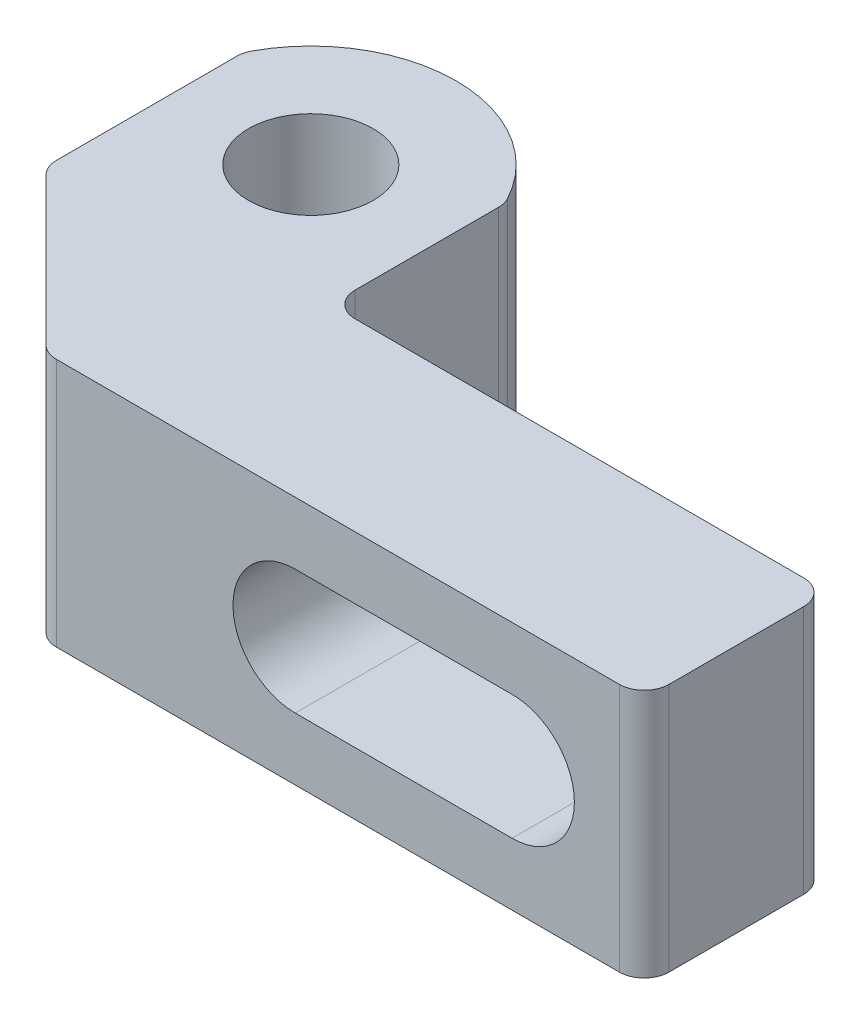
SolidWorks part; units mm, degrees
ref_plane "Front Plane" through (0, 0, 0) normal (0, 0, 1) x (1, 0, 0)
ref_plane "Top Plane" through (0, 0, 0) normal (0, 1, 0) x (1, 0, 0)
ref_plane "Right Plane" through (0, 0, 0) normal (1, 0, 0) x (0, 0, -1)
sketch "Sketch1" plane through (0, 0, 0) normal (0, 1, 0) x (1, 0, 0)
  line L0 (0, 0) -> (0, 7.4)
  line L1 (0, 7.4) -> (-20, 7.4)
  line L2 (-20, 7.4) -> (-20, 14.4)
  line L3 (0, 0) -> (-24, 0)
  line L4 (-24, 0) -> (-30.5, 6.5)
  line L5 (-30.5, 6.5) -> (-30.5, 14.4)
  line L6 (-30.5, 14.4) -> (-20, 14.4) construction
  arc A0 (-30.5, 14.4) -> (-20, 14.4) centre (-25.25, 11.8739) cw
  circle A1 centre (-25.25, 11.8739) radius 2.5
  dimension "D7" = 3.3
  dimension "D8" = 5
  dimension "D1" = 7.4
  dimension "D2" = 10.5
  dimension "D3" = 20
  dimension "D4" = 24
  dimension "D5" = 135
  dimension "D6" = 7
extrude "Boss-Extrude1" add sketch "Sketch1" along normal blind 10
sketch "Sketch3" plane through (0, 0, -7.4) normal (0, 0, -1) x (-1, 0, 0)
  line L0 (20, 5) -> (0, 5) construction
  line L1 (20, 10) -> (20, 0) construction
  line L2 (0, 10) -> (0, 0) construction
  line L3 (14, 5) -> (5.3, 5) construction
  line L4 (14, 2.5) -> (5.3, 2.5)
  line L5 (14, 7.5) -> (5.3, 7.5)
  arc A0 (14, 2.5) -> (14, 7.5) centre (14, 5) ccw
  arc A1 (5.3, 7.5) -> (5.3, 2.5) centre (5.3, 5) ccw
  point P8 (9.65, 5)
  point P13 (4.008, 5)
  dimension "D1" = 5
  dimension "D2" = 2.8
  dimension "D3" = 3.5
extrude "Cut-Extrude1" cut sketch "Sketch3" against normal through all
fillet "Fillet2" radius 1 7 edges at (-24, 5, 0) (-30.5, 5, -6.5) (-30.5, 5, -14.4) (-20, 5, -14.4) (-20, 5, -7.4) (0, 5, -7.4) (0, 5, 0)
